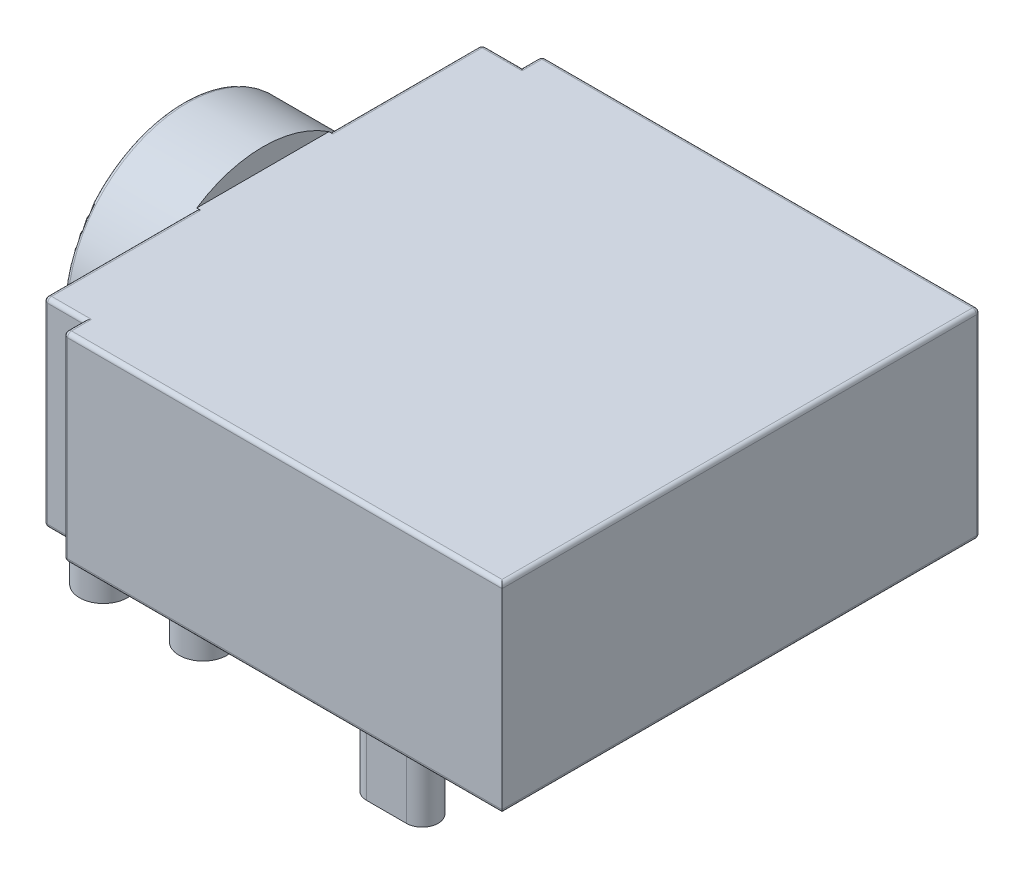
SolidWorks part; units mm, degrees
ref_plane "Спереди" through (0, 0, 0) normal (0, 0, 1) x (1, 0, 0)
ref_plane "Сверху" through (0, 0, 0) normal (0, 1, 0) x (1, 0, 0)
ref_plane "Справа" through (0, 0, 0) normal (1, 0, 0) x (0, 0, -1)
sketch "Эскиз1" plane through (0, 0, 0) normal (0, 1, 0) x (1, 0, 0)
  line L1 (-5.5, 6) -> (5.5, 6)
  line L2 (-5.5, 6) -> (-5.5, -6)
  line L3 (-5.5, -6) -> (5.5, -6)
  line L4 (5.5, 6) -> (5.5, -6)
  line L5 (-5.5, 6) -> (5.5, -6) construction
  line L6 (-5.5, -6) -> (5.5, 6) construction
  point P0 (0, 0)
  dimension "D1" = 11
  dimension "D2" = 12
extrude "Бобышка-Вытянуть1" add sketch "Эскиз1" along normal blind 5
sketch "Эскиз2" plane through (-5.5, 0, 0) normal (-1, 0, 0) x (0, 0, 1)
  line L0 (0, 0) -> (0, 5) construction
  line L1 (-6, 5) -> (6, 5) construction
  line L2 (-6, 2.5) -> (6, 2.5) construction
  line L3 (-6, 5) -> (-6, 0) construction
  line L4 (6, 5) -> (6, 0) construction
  line L6 (-5.5, 5) -> (5.5, 5)
  line L7 (-5.5, 5) -> (-5.5, 0)
  line L8 (-5.5, 0) -> (5.5, 0)
  line L9 (5.5, 5) -> (5.5, 0)
  line L10 (-5.5, 5) -> (5.5, 0) construction
  line L11 (-5.5, 0) -> (5.5, 5) construction
  point P11 (0, 2.5)
  dimension "D1" = 11
  dimension "D2" = 5
extrude "Бобышка-Вытянуть2" add sketch "Эскиз2" along normal blind 1
sketch "Эскиз3" plane through (-6.5, 0, 0) normal (-1, 0, 0) x (0, 0, 1)
  line L0 (-5.5, 0) -> (5.5, 5) construction
  line L1 (-5.5, 5) -> (5.5, 0) construction
  circle A0 centre (0, 2.5) radius 3
  dimension "D1" = 6
extrude "Бобышка-Вытянуть3" add sketch "Эскиз3" along normal blind 2
sketch "Эскиз4" plane through (-8.5, 0, 0) normal (-1, 0, 0) x (0, 0, 1)
  circle A0 centre (0, 2.5) radius 1.8
  dimension "D1" = 3.6
extrude "Вырез-Вытянуть1" cut sketch "Эскиз4" against normal blind 2
fillet "Скругление1" radius 0.1 2 edges at (-8.5, 2.5, 3) (-8.5, 2.5, 1.8)
fillet "Скругление2" radius 0.1 23 edges at (0, 0, 6) (0, 5, 6) (-5.5, 5, -5.75) (-5.5, 0, -5.75) (-6, 0, -5.5) (-5.5, 0, 5.75) (-5.5, 5, 5.75) (-6, 0, 5.5) (-6.5, 0, 3.5792) (-6.5, 0, -3.5792) (0, 0, -6) (0, 5, -6) (5.5, 0, 0) (5.5, 5, 0) (5.5, 2.5, -6) (-5.5, 2.5, -6) (-6.5, 2.5, -5.5) (-6.5, 2.5, 5.5) (-5.5, 2.5, 6) (-6, 5, 5.5) (-6.5, 5, 3.5792) (-6.5, 5, -3.5792) (-6, 5, -5.5)
sketch "Эскиз5" plane through (0, 0, 0) normal (0, -1, 0) x (1, 0, 0)
  line L0 (-6.5, 0) -> (5.4, 0) construction
  line L1 (-6.5, -1.6583) -> (-6.5, 1.6583) construction
  line L2 (5.4, -5.9) -> (5.4, 5.9) construction
  line L3 (0, 5.9) -> (0, -5.9) construction
  line L4 (5.4, 5.9) -> (-5.4, 5.9) construction
  line L5 (-5.4, -5.9) -> (5.4, -5.9) construction
  line L6 (2, 5.9) -> (2, -5.9) construction
  line L7 (-6.5, -1.6583) -> (-6.5, 1.6583) construction
  line L8 (-6.4, -5) -> (5.4, -5) construction
  line L9 (-6.4, -1.6583) -> (-6.4, -5.4) construction
  line L10 (-6.4, 5) -> (5.4, 5) construction
  line L11 (-3, 5.9) -> (-3, -5.9) construction
  line L12 (-6.4, 5.4) -> (-6.4, 1.6583) construction
  line L13 (1.5, 5) -> (2.5, 5) construction
  line L14 (1.5, 5.4) -> (2.5, 5.4)
  line L15 (1.5, 4.6) -> (2.5, 4.6)
  line L16 (1.5, -5) -> (2.5, -5) construction
  line L17 (1.5, -4.6) -> (2.5, -4.6)
  line L18 (1.5, -5.4) -> (2.5, -5.4)
  line L19 (1.5, 2.5) -> (2.5, 2.5) construction
  line L20 (1.5, 2.9) -> (2.5, 2.9)
  line L21 (1.5, 2.1) -> (2.5, 2.1)
  line L22 (1.5, -2.5) -> (2.5, -2.5) construction
  line L23 (1.5, -2.1) -> (2.5, -2.1)
  line L24 (1.5, -2.9) -> (2.5, -2.9)
  line L25 (-3, -0.5) -> (-3, 0.5) construction
  line L26 (-3.4, -0.5) -> (-3.4, 0.5)
  line L27 (-2.6, -0.5) -> (-2.6, 0.5)
  line L28 (-6.4, 2.5) -> (5.4, 2.5) construction
  line L29 (-6.4, -2.5) -> (5.4, -2.5) construction
  arc A0 (1.5, 5.4) -> (1.5, 4.6) centre (1.5, 5) ccw
  arc A1 (2.5, 4.6) -> (2.5, 5.4) centre (2.5, 5) ccw
  arc A2 (1.5, -4.6) -> (1.5, -5.4) centre (1.5, -5) ccw
  arc A3 (2.5, -5.4) -> (2.5, -4.6) centre (2.5, -5) ccw
  arc A4 (1.5, 2.9) -> (1.5, 2.1) centre (1.5, 2.5) ccw
  arc A5 (2.5, 2.1) -> (2.5, 2.9) centre (2.5, 2.5) ccw
  arc A6 (1.5, -2.1) -> (1.5, -2.9) centre (1.5, -2.5) ccw
  arc A7 (2.5, -2.9) -> (2.5, -2.1) centre (2.5, -2.5) ccw
  arc A8 (-3.4, -0.5) -> (-2.6, -0.5) centre (-3, -0.5) ccw
  arc A9 (-2.6, 0.5) -> (-3.4, 0.5) centre (-3, 0.5) ccw
  point P26 (2, 5)
  point P34 (2, -5)
  point P42 (2, 2.5)
  point P49 (2, -2.5)
  point P56 (-3, 0)
  dimension "D2" = 5
  dimension "D3" = 2.5
  dimension "D1" = 8.5
  dimension "D4" = 2.5
extrude "Бобышка-Вытянуть4" add sketch "Эскиз5" along normal blind 2
sketch "Эскиз6" plane through (0, 0, 0) normal (0, -1, 0) x (1, 0, 0)
  line L0 (-6.5, 0) -> (5.4, 0) construction
  line L1 (-6.5, -1.6583) -> (-6.5, 1.6583) construction
  line L2 (5.4, -5.9) -> (5.4, 5.9) construction
  line L3 (5.4, 5.9) -> (-5.4, 5.9) construction
  line L4 (-5.5, -5.9) -> (-5.5, 5.9) construction
  line L5 (-5.4, -5.9) -> (5.4, -5.9) construction
  line L6 (-3, -5.9) -> (-3, 5.9) construction
  circle A0 centre (-3, 5) radius 0.6
  circle A1 centre (-3, -5) radius 0.6
  circle A2 centre (2.0235, 0) radius 0.6
  circle A3 centre (-5.5, 5) radius 0.6
  circle A4 centre (-5.5, -5) radius 0.6
  dimension "D2" = 1.2
  dimension "D3" = 1.2
  dimension "D4" = 1.2
  dimension "D5" = 1.2
  dimension "D6" = 1.2
  dimension "D1" = 2.5
extrude "Бобышка-Вытянуть5" add sketch "Эскиз6" along normal blind 1
